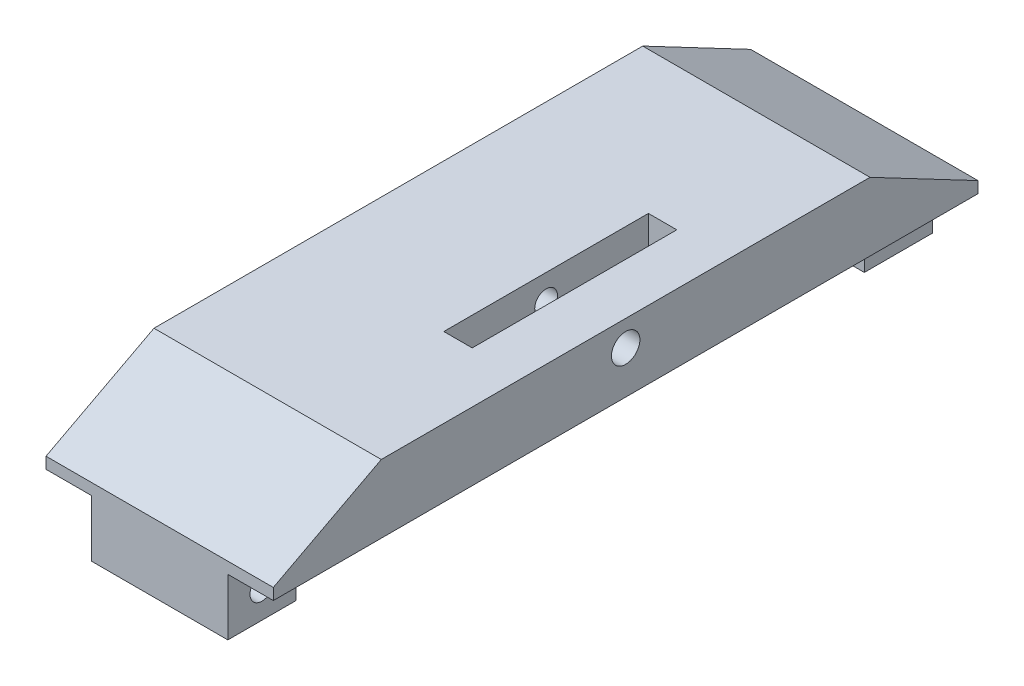
SolidWorks part; units mm, degrees
ref_plane "Спереди" through (0, 0, 0) normal (0, 0, 1) x (1, 0, 0)
ref_plane "Сверху" through (0, 0, 0) normal (0, 1, 0) x (1, 0, 0)
ref_plane "Справа" through (0, 0, 0) normal (1, 0, 0) x (0, 0, -1)
ref_plane "Плоскость4" through (0, 70, 0) normal (0, 1, 0) x (1, 0, 0)
sketch "Эскиз1" plane through (0, 70, 0) normal (0, 1, 0) x (1, 0, 0)
  line L0 (20, -62) -> (-20, -62)
  line L2 (-20, 38.5) -> (-20, -38.5) construction
  line L3 (-13, -62) -> (-20, -62) construction
  line L4 (20, -62) -> (20, 62)
  line L5 (20, 62) -> (13, 62) construction
  line L6 (20, 18) -> (20, 62) construction
  line L7 (20, 62) -> (-20, 62)
  line L8 (-13, 62) -> (-20, 62) construction
  line L9 (-20, 62) -> (-20, -62)
  line L10 (6, 18) -> (6, -18)
  line L11 (6, -18) -> (11, -18)
  line L12 (20, -18) -> (6, -18) construction
  line L13 (11, -18) -> (11, 18)
  line L14 (6, 18) -> (20, 18) construction
  line L15 (11, 18) -> (6, 18)
extrude "Бобышка-Вытянуть1" add sketch "Эскиз1" along normal blind 2
ref_plane "Плоскость5" through (0, 72, 0) normal (0, 1, 0) x (1, 0, 0)
sketch "Эскиз2" plane through (0, 72, 0) normal (0, 1, 0) x (1, 0, 0)
  line L0 (6, 18) -> (-20, 18)
  line L3 (6, -18) -> (-20, -18)
  line L4 (-20, -18) -> (-20, 18)
  line L5 (6, 18) -> (6, -18)
extrude "Бобышка-Вытянуть2" add sketch "Эскиз2" along normal blind 10
ref_plane "Плоскость6" through (-20, 0, 0) normal (-1, 0, 0) x (0, 0, 1)
sketch "Эскиз3" plane through (-20, 0, 0) normal (-1, 0, 0) x (0, 0, 1)
  circle A0 centre (0, 77.5) radius 2.5
  circle A1 centre (0, 77.5) radius 3
  circle A2 centre (0, 77.5) radius 2
  point P0 (0, 0)
extrude "Вырез-Вытянуть1" cut sketch "Эскиз3" against normal blind 26 contours A2 region at (-20, 77.5, 0)
extrude "Вырез-Вытянуть2" cut sketch "Эскиз3<3>" against normal blind 16 contours A0 A2 region at (-20, 77.5, -2.4293)
sketch "Эскиз3<3>" plane through (-20, 0, 0) normal (-1, 0, 0) x (0, 0, 1) same geometry as "Эскиз3"
extrude "Вырез-Вытянуть3" cut sketch "Эскиз3<4>" against normal blind 8 contours A1 A0 region at (-20, 77.5, -2.9151)
sketch "Эскиз3<4>" plane through (-20, 0, 0) normal (-1, 0, 0) x (0, 0, 1) same geometry as "Эскиз3"
sketch "Эскиз4" plane through (0, 72, 0) normal (0, 1, 0) x (1, 0, 0)
  line L0 (11, -18) -> (20, -18)
  line L1 (20, -62) -> (20, 62) construction
  line L2 (11, 18) -> (20, 18)
  line L3 (20, 18) -> (20, -18)
  line L4 (11, -18) -> (11, 18)
extrude "Бобышка-Вытянуть3" add sketch "Эскиз4" along normal blind 10
ref_plane "Плоскость7" through (20, 0, 0) normal (1, 0, 0) x (0, 0, -1)
sketch "Эскиз5" plane through (20, 0, 0) normal (1, 0, 0) x (0, 0, -1)
  circle A0 centre (0, 77.5) radius 1.5
  circle A1 centre (0, 77.5) radius 2.5
  point P0 (0, 0)
extrude "Вырез-Вытянуть4" cut sketch "Эскиз5" against normal blind 9 contours A0 region at (20, 77.5, 0)
extrude "Вырез-Вытянуть5" cut sketch "Эскиз5<3>" against normal blind 6
sketch "Эскиз5<3>" plane through (20, 0, 0) normal (1, 0, 0) x (0, 0, -1) same geometry as "Эскиз5"
sketch "Эскиз6" plane through (20, 0, 0) normal (1, 0, 0) x (0, 0, -1)
  line L0 (-18, 82) -> (-43, 82)
  line L1 (-43, 82) -> (-62, 72)
  line L2 (55, 72) -> (-55, 72) construction
  line L3 (-62, 72) -> (-62, 70) construction
  line L4 (-62, 72) -> (-18, 72)
  line L5 (-18, 72) -> (-18, 82)
  line L6 (18, 82) -> (43, 82)
  line L7 (43, 82) -> (62, 72)
  line L8 (62, 72) -> (18, 72)
  line L9 (18, 72) -> (18, 82)
extrude "Бобышка-Вытянуть4" add sketch "Эскиз6" against normal blind 40
ref_plane "Плоскость9" through (-12, 0, 0) normal (1, 0, 0) x (0, 0, -1)
sketch "Эскиз7" plane through (-12, 0, 0) normal (1, 0, 0) x (0, 0, -1)
  line L0 (-62, 60) -> (-50, 60)
  line L1 (-50, 40) -> (-50, 70) construction
  line L2 (-50, 60) -> (-50, 70)
  line L3 (22, 70) -> (-22, 70) construction
  line L4 (-50, 70) -> (-62, 70)
  line L5 (-62, 70) -> (-62, 60)
  line L6 (50, 70) -> (50, 60)
  line L7 (50, 40) -> (50, 70) construction
  line L8 (50, 60) -> (62, 60)
  line L9 (62, 60) -> (62, 70)
  line L10 (62, 70) -> (62, 60) construction
  line L11 (62, 70) -> (50, 70)
  circle A0 centre (56, 65) radius 2.1
  circle A1 centre (-56, 65) radius 2.1
extrude "Бобышка-Вытянуть5" add sketch "Эскиз7" along normal blind 24
fillet "Скругление1" radius 2 4 edges at (8.5, 70, -18) (11, 70, 0) (8.5, 70, 18) (6, 70, 0) conic rho 0.5
